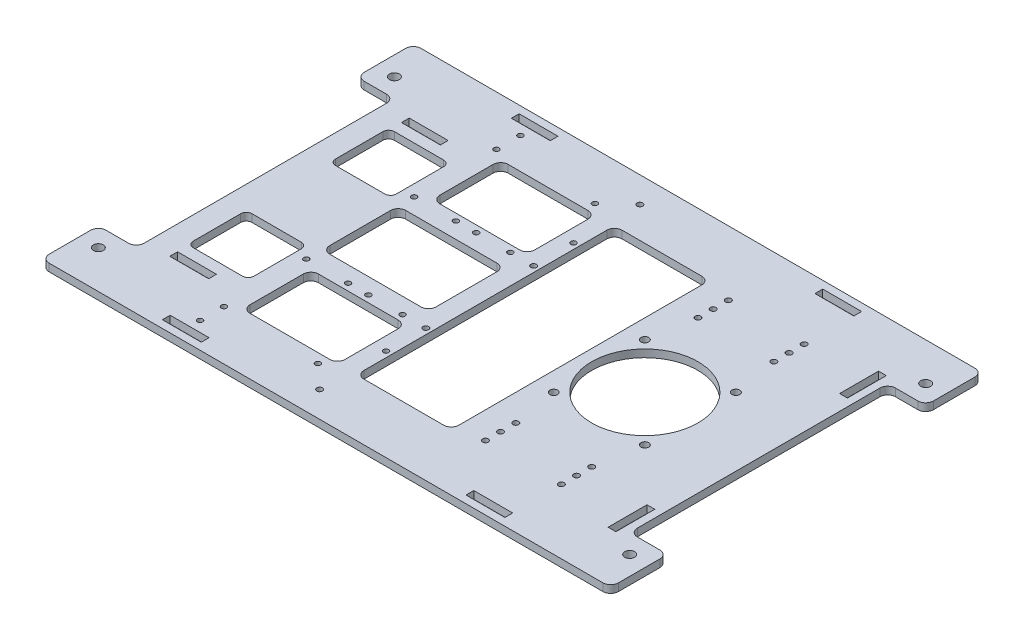
SolidWorks part; units mm, degrees
ref_plane "Спереди" through (0, 0, 0) normal (0, 0, 1) x (1, 0, 0)
ref_plane "Сверху" through (0, 0, 0) normal (0, 1, 0) x (1, 0, 0)
ref_plane "Справа" through (0, 0, 0) normal (1, 0, 0) x (0, 0, -1)
other "Configuration Table"
sketch "Эскиз1" plane through (0, 0, 0) normal (0, 1, 0) x (1, 0, 0)
  line L0 (0, -170.1085) -> (0, -191.8915)
  line L1 (4.1085, 0) -> (295.8915, 0)
  line L2 (0, -4.1085) -> (0, -25.8915)
  line L3 (4.1085, -196) -> (295.8915, -196)
  line L4 (300, -4.1085) -> (300, -25.8915)
  line L5 (4.1085, -30) -> (15.8915, -30)
  line L7 (4.1085, -166) -> (15.8915, -166)
  line L8 (20, -34.1085) -> (20, -161.8915)
  line L9 (295.8915, -30) -> (284.1085, -30)
  line L11 (295.8915, -166) -> (284.1085, -166)
  line L12 (280, -34.1085) -> (280, -161.8915)
  line L13 (300, -170.1085) -> (300, -191.8915)
  line L14 (-22.5077, -98) -> (393.8408, -98) construction
  circle A0 centre (220, -98) radius 28
  arc A1 (295.8915, -30) -> (300, -25.8915) centre (295.8915, -25.8915) ccw
  arc A2 (295.8915, 0) -> (300, -4.1085) centre (295.8915, -4.1085) cw
  arc A3 (284.1085, -30) -> (280, -34.1085) centre (284.1085, -34.1085) ccw
  arc A4 (284.1085, -166) -> (280, -161.8915) centre (284.1085, -161.8915) cw
  arc A5 (300, -170.1085) -> (295.8915, -166) centre (295.8915, -170.1085) ccw
  arc A6 (295.8915, -196) -> (300, -191.8915) centre (295.8915, -191.8915) ccw
  arc A7 (0, -191.8915) -> (4.1085, -196) centre (4.1085, -191.8915) ccw
  arc A8 (0, -170.1085) -> (4.1085, -166) centre (4.1085, -170.1085) cw
  arc A9 (15.8915, -166) -> (20, -161.8915) centre (15.8915, -161.8915) ccw
  arc A10 (15.8915, -30) -> (20, -34.1085) centre (15.8915, -34.1085) cw
  arc A11 (4.1085, -30) -> (0, -25.8915) centre (4.1085, -25.8915) cw
  arc A12 (4.1085, 0) -> (0, -4.1085) centre (4.1085, -4.1085) ccw
  circle A13 centre (10, -20) radius 2.6
  circle A14 centre (290, -20) radius 2.6
  circle A15 centre (290, -176) radius 2.6
  circle A16 centre (10, -176) radius 2.6
  point P19 (300, -30)
  point P22 (300, 0)
  point P25 (280, -30)
  point P34 (0, -196)
  point P41 (20, -30)
  point P44 (0, -30)
  point P47 (0, 0)
  dimension "D8" = 56
  dimension "D10" = 4.1085
  dimension "D11" = 5.2
  dimension "D12" = 5.2
  dimension "D1" = 300
  dimension "D2" = 196
  dimension "D3" = 20
  dimension "D4" = 30
  dimension "D5" = 30
  dimension "D6" = 20
  dimension "D7" = 98
  dimension "D9" = 60
  dimension "D13" = 10
  dimension "D14" = 10
  dimension "D15" = 10
  dimension "D16" = 10
base flange "Базовая кромка1" sketch "Эскиз1" thickness 4 reverse thickness direction no parameters "D1"=4
sketch "Эскиз6" plane through (0, 0, 0) normal (0, 1, 0) x (1, 0, 0)
  line L0 (0, -98) -> (316.488, -98) construction
  line L1 (271.9, -26.75) -> (276, -26.75)
  line L2 (271.9, -26.75) -> (271.9, -47.25)
  line L3 (271.9, -47.25) -> (276, -47.25)
  line L4 (276, -26.75) -> (276, -47.25)
  line L5 (219.75, -4) -> (240.25, -4)
  line L6 (219.75, -4) -> (219.75, -8.1)
  line L7 (219.75, -8.1) -> (240.25, -8.1)
  line L8 (240.25, -4) -> (240.25, -8.1)
  line L9 (59.75, -4) -> (80.25, -4)
  line L10 (59.75, -4) -> (59.75, -8.1)
  line L11 (59.75, -8.1) -> (80.25, -8.1)
  line L12 (80.25, -4) -> (80.25, -8.1)
  line L21 (295.8915, 0) -> (4.1085, 0) construction
  line L22 (280, -161.8915) -> (280, -34.1085) construction
  line L23 (20, -34.1085) -> (20, -161.8915) construction
  line L24 (32.75, -34.9) -> (53.25, -34.9)
  line L25 (32.75, -34.9) -> (32.75, -39)
  line L26 (32.75, -39) -> (53.25, -39)
  line L27 (53.25, -34.9) -> (53.25, -39)
  line L28 (53.25, -161.1) -> (53.25, -157)
  line L29 (32.75, -157) -> (53.25, -157)
  line L30 (32.75, -161.1) -> (32.75, -157)
  line L31 (32.75, -161.1) -> (53.25, -161.1)
  line L32 (80.25, -192) -> (80.25, -187.9)
  line L33 (59.75, -187.9) -> (80.25, -187.9)
  line L34 (59.75, -192) -> (59.75, -187.9)
  line L35 (59.75, -192) -> (80.25, -192)
  line L36 (240.25, -192) -> (240.25, -187.9)
  line L37 (219.75, -187.9) -> (240.25, -187.9)
  line L38 (219.75, -192) -> (219.75, -187.9)
  line L39 (219.75, -192) -> (240.25, -192)
  line L40 (276, -169.25) -> (276, -148.75)
  line L41 (271.9, -148.75) -> (276, -148.75)
  line L42 (271.9, -169.25) -> (271.9, -148.75)
  line L43 (271.9, -169.25) -> (276, -169.25)
  dimension "D1" = 98
  dimension "D2" = 20.5
  dimension "D3" = 20.5
  dimension "D4" = 20.5
  dimension "D5" = 4.1
  dimension "D6" = 4
  dimension "D7" = 4
  dimension "D8" = 4
  dimension "D9" = 20.5
  dimension "D10" = 4.1
  dimension "D11" = 39.75
  dimension "D12" = 39.75
  dimension "D13" = 35
  dimension "D14" = 12.75
  dimension "D15" = 26.75
extrude "Вырез-Вытянуть1" cut sketch "Эскиз6" against normal up to next normal cut yes
sketch "Эскиз7" plane through (0, 0, 0) normal (0, 1, 0) x (1, 0, 0)
  line L0 (4.1085, 0) -> (295.8915, 0) construction
  line L1 (140, -30) -> (182, -30)
  line L2 (136, -34) -> (136, -162)
  line L3 (140, -166) -> (182, -166)
  line L4 (186, -34) -> (186, -162)
  line L5 (4.1085, -196) -> (295.8915, -196) construction
  line L6 (280, -34.1085) -> (280, -161.8915) construction
  line L7 (20, -34.1085) -> (20, -161.8915) construction
  line L8 (74, -78) -> (122, -78)
  line L9 (70, -82) -> (70, -114)
  line L10 (74, -118) -> (122, -118)
  line L11 (126, -82) -> (126, -114)
  line L12 (-22.5077, -98) -> (393.8408, -98) construction
  line L14 (32.75, -39) -> (53.25, -39) construction
  line L15 (35, -45) -> (61, -45)
  line L16 (32, -48) -> (32, -73)
  line L17 (35, -76) -> (61, -76)
  line L18 (64, -48) -> (64, -73)
  line L19 (20, -34.1085) -> (20, -161.8915) construction
  line L20 (220, -98) -> (-41.1636, -98) construction
  line L21 (64, -148) -> (64, -123)
  line L22 (35, -120) -> (61, -120)
  line L23 (32, -148) -> (32, -123)
  line L24 (35, -151) -> (61, -151)
  arc A0 (136, -162) -> (140, -166) centre (140, -162) ccw
  arc A1 (182, -166) -> (186, -162) centre (182, -162) ccw
  arc A2 (182, -30) -> (186, -34) centre (182, -34) cw
  arc A3 (140, -30) -> (136, -34) centre (140, -34) ccw
  arc A4 (122, -78) -> (126, -82) centre (122, -82) cw
  arc A5 (122, -118) -> (126, -114) centre (122, -114) ccw
  arc A6 (70, -114) -> (74, -118) centre (74, -114) ccw
  arc A7 (74, -78) -> (70, -82) centre (74, -82) ccw
  circle A8 centre (196, -74) radius 2.05
  circle A9 centre (220, -98) radius 28 construction
  circle A10 centre (244, -74) radius 2.05
  circle A11 centre (244, -122) radius 2.05
  circle A12 centre (196, -122) radius 2.05
  arc A13 (61, -76) -> (64, -73) centre (61, -73) ccw
  arc A14 (61, -45) -> (64, -48) centre (61, -48) cw
  arc A15 (35, -45) -> (32, -48) centre (35, -48) ccw
  arc A16 (32, -73) -> (35, -76) centre (35, -73) ccw
  arc A17 (32, -123) -> (35, -120) centre (35, -123) cw
  arc A18 (35, -151) -> (32, -148) centre (35, -148) cw
  arc A19 (61, -151) -> (64, -148) centre (61, -148) ccw
  arc A20 (61, -120) -> (64, -123) centre (61, -123) cw
  point P24 (186, -30)
  point P27 (136, -30)
  point P61 (64, -45)
  point P64 (32, -45)
  point P79 (32, -151)
  point P80 (64, -151)
  dimension "D9" = 4
  dimension "D12" = 4.1
  dimension "D18" = 3
  dimension "D1" = 30
  dimension "D2" = 30
  dimension "D3" = 94
  dimension "D4" = 50
  dimension "D5" = 50
  dimension "D6" = 40
  dimension "D7" = 20
  dimension "D8" = 10
  dimension "D10" = 24
  dimension "D11" = 24
  dimension "D14" = 22
  dimension "D15" = 6
  dimension "D16" = 12
  dimension "D17" = 32
  dimension "D13" = 2
extrude "Вырез-Вытянуть2" cut sketch "Эскиз7" against normal up to next normal cut yes
sketch "Эскиз14" plane through (0, 0, 0) normal (0, 1, 0) x (1, 0, 0)
  line L0 (295.8915, 0) -> (4.1085, 0) construction
  line L2 (0, -98) -> (328.8146, -98) construction
  line L5 (20, -34.1085) -> (20, -161.8915) construction
  line L6 (122, -78) -> (74, -78) construction
  line L7 (80, -30) -> (122, -30)
  line L8 (76, -34) -> (76, -62)
  line L9 (80, -66) -> (122, -66)
  line L10 (126, -34) -> (126, -62)
  line L11 (136, -34) -> (136, -162) construction
  line L12 (126, -162) -> (126, -134)
  line L13 (80, -130) -> (122, -130)
  line L14 (76, -162) -> (76, -134)
  line L15 (80, -166) -> (122, -166)
  circle A0 centre (70, -26.2) radius 1.4
  circle A1 centre (120.7, -25) radius 1.4
  circle A2 centre (70, -69.6) radius 1.4
  circle A3 centre (120.7, -69.6) radius 1.4
  circle A4 centre (70, -13.6) radius 1.4
  circle A5 centre (133, -13.6) radius 1.4947
  circle A6 centre (133, -69.6) radius 1.4762
  circle A7 centre (133, -126.4) radius 1.4762
  circle A8 centre (133, -182.4) radius 1.4947
  circle A9 centre (70, -182.4) radius 1.4
  circle A10 centre (120.7, -126.4) radius 1.4
  circle A11 centre (70, -126.4) radius 1.4
  circle A12 centre (120.7, -171) radius 1.4
  circle A13 centre (70, -169.8) radius 1.4
  arc A14 (122, -30) -> (126, -34) centre (122, -34) cw
  arc A15 (122, -66) -> (126, -62) centre (122, -62) ccw
  arc A16 (76, -62) -> (80, -66) centre (80, -62) ccw
  arc A17 (80, -30) -> (76, -34) centre (80, -34) ccw
  arc A18 (80, -166) -> (76, -162) centre (80, -162) cw
  arc A19 (76, -134) -> (80, -130) centre (80, -134) cw
  arc A20 (122, -130) -> (126, -134) centre (122, -134) cw
  arc A21 (122, -166) -> (126, -162) centre (122, -162) ccw
  circle A22 centre (133, -48.6) radius 1.4
  circle A23 centre (92, -69.6) radius 1.4
  circle A24 centre (61.7, -48.6) radius 1.4
  circle A25 centre (102.7, -69.6) radius 1.4
  circle A26 centre (102.7, -126.4) radius 1.4
  circle A27 centre (92, -126.4) radius 1.4
  circle A28 centre (133, -147.4) radius 1.4
  circle A29 centre (61.7, -147.4) radius 1.4
  point P46 (126, -66)
  point P49 (76, -66)
  point P64 (76, -130)
  point P65 (126, -130)
  dimension "D2" = 2.8
  dimension "D14" = 4
  dimension "D1" = 50.7
  dimension "D3" = 43.4
  dimension "D4" = 44.6
  dimension "D5" = 25
  dimension "D6" = 50
  dimension "D7" = 98
  dimension "D8" = 56
  dimension "D9" = 63
  dimension "D10" = 50
  dimension "D11" = 30
  dimension "D12" = 12
  dimension "D13" = 10
  dimension "D15" = 21
  dimension "D16" = 41
  dimension "D17" = 21
  dimension "D18" = 41
  dimension "D19" = 18
extrude "Вырез-Вытянуть3" cut sketch "Эскиз14" against normal through all normal cut yes
sketch "Эскиз15" plane through (0, 0, 0) normal (0, 1, 0) x (1, 0, 0)
  line L0 (295.8915, 0) -> (4.1085, 0) construction
  line L1 (300, -25.8915) -> (300, -4.1085) construction
  line L2 (248, -98) -> (358.3996, -98) construction
  circle A0 centre (200, -34) radius 1.5
  circle A1 centre (240, -34) radius 1.5
  circle A2 centre (240, -42) radius 1.5
  circle A3 centre (240, -50) radius 1.5
  circle A4 centre (200, -42) radius 1.5
  circle A5 centre (200, -50) radius 1.5
  circle A6 centre (220, -98) radius 28 construction
  circle A7 centre (200, -146) radius 1.5
  circle A8 centre (200, -154) radius 1.5
  circle A9 centre (240, -146) radius 1.5
  circle A10 centre (240, -154) radius 1.5
  circle A11 centre (240, -162) radius 1.5
  circle A12 centre (200, -162) radius 1.5
  dimension "D3" = 3
  dimension "D4" = 3
  dimension "D1" = 34
  dimension "D2" = 100
  dimension "D5" = 2
extrude "Вырез-Вытянуть4" cut sketch "Эскиз15" against normal through all normal cut yes
sketch "Сгиб-Линии1" [suppressed] plane through (0, 0, 0) normal (0, 1, 0) x (1, 0, 0)
sketch "Граничная рамка1" [suppressed] plane through (0, 0, 0) normal (0, 1, 0) x (1, 0, 0)
sheet metal parameters "Листовой металл3" thickness 4 parameters "D1"=4
flat pattern "Развертка3" [suppressed]
sketch "Сгиб-Линии2" plane through (0, 0, 0) normal (0, 1, 0) x (1, 0, 0)
sketch "Граничная рамка2" [suppressed] plane through (0, 0, 0) normal (0, 1, 0) x (1, 0, 0)
sheet metal parameters "Листовой металл4" thickness 4 parameters "D1"=4
flat pattern "Развертка3"
sketch "Сгиб-Линии2" plane through (0, 0, 0) normal (0, 1, 0) x (1, 0, 0)
sketch "Граничная рамка2" [suppressed] plane through (0, 0, 0) normal (0, 1, 0) x (1, 0, 0)
sheet metal parameters "Листовой металл5" thickness 4 parameters "D1"=4
flat pattern "Развертка3"
sketch "Сгиб-Линии2" plane through (0, 0, 0) normal (0, 1, 0) x (1, 0, 0)
sketch "Граничная рамка2" [suppressed] plane through (0, 0, 0) normal (0, 1, 0) x (1, 0, 0)
sheet metal parameters "Листовой металл6" thickness 4 parameters "D1"=4
flat pattern "Развертка6"
sketch "Сгиб-Линии3" plane through (0, 0, 0) normal (0, 1, 0) x (1, 0, 0)
sketch "Граничная рамка3" [suppressed] plane through (0, 0, 0) normal (0, 1, 0) x (1, 0, 0)
sheet metal parameters "Листовой металл7" thickness 4 parameters "D1"=4
flat pattern "Развертка7"
sketch "Сгиб-Линии4" plane through (0, 0, 0) normal (0, 1, 0) x (1, 0, 0)
sketch "Граничная рамка4" [suppressed] plane through (0, 0, 0) normal (0, 1, 0) x (1, 0, 0)
sheet metal parameters "Листовой металл8" thickness 4 parameters "D1"=4
flat pattern "Развертка3"
sketch "Сгиб-Линии2" plane through (0, 0, 0) normal (0, 1, 0) x (1, 0, 0)
sketch "Граничная рамка2" [suppressed] plane through (0, 0, 0) normal (0, 1, 0) x (1, 0, 0)
sheet metal parameters "Листовой металл9" thickness 4 parameters "D1"=4
flat pattern "Развертка3"
sketch "Сгиб-Линии2" plane through (0, 0, 0) normal (0, 1, 0) x (1, 0, 0)
sketch3d "Граничная рамка2" [suppressed]
  line L0 (-295.8915, -170.1084, 0) -> (4.1085, -170.1085, 0) construction
  line L1 (-295.8915, 25.8915, 0) -> (4.1085, 25.8915, 0) construction
  line L2 (-295.8915, -170.1084, 0) -> (-295.8915, 25.8915, 0) construction
  line L3 (4.1085, -170.1085, 0) -> (4.1085, 25.8915, 0) construction
